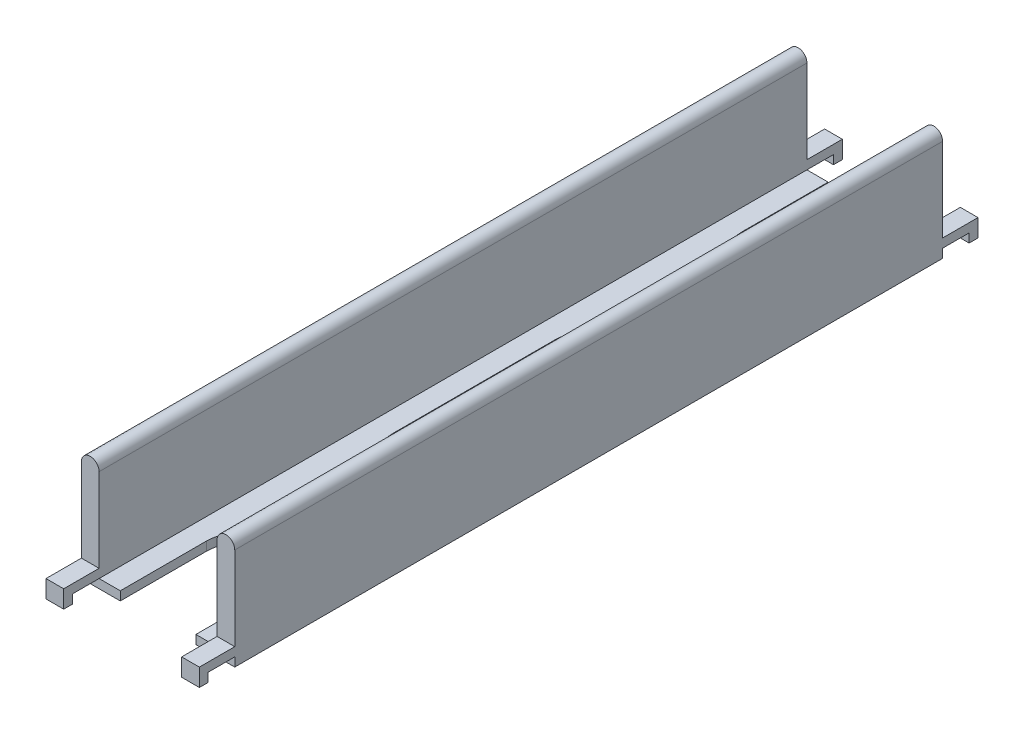
SolidWorks part; units mm, degrees
ref_plane "Front Plane" through (0, 0, 0) normal (0, 0, 1) x (1, 0, 0)
ref_plane "Top Plane" through (0, 0, 0) normal (0, 1, 0) x (1, 0, 0)
ref_plane "Right Plane" through (0, 0, 0) normal (1, 0, 0) x (0, 0, -1)
sketch "Sketch1" plane through (0, 0, 0) normal (0, 1, 0) x (1, 0, 0)
  line L0 (-3.3333, 20) -> (-3.3333, -20)
  line L1 (-4.3333, -20) -> (4.3333, -20)
  line L2 (-4.3333, -20) -> (-4.3333, 20)
  line L3 (-4.3333, 20) -> (4.3333, 20)
  line L4 (4.3333, -20) -> (4.3333, 20)
  line L5 (-4.3333, -20) -> (4.3333, 20) construction
  line L6 (-4.3333, 20) -> (4.3333, -20) construction
  line L7 (3.3333, 20) -> (3.3333, -20)
  point P0 (0, 0)
  dimension "D1" = 8.6667
  dimension "D2" = 40
  dimension "D3" = 1
  dimension "D4" = 1
extrude "Boss-Extrude1" add sketch "Sketch1" along normal blind 0.5 contours L7 L3 L0 L1 region at (0, 0, 0)
extrude "Boss-Extrude2" add sketch "Sketch1<3>" along normal blind 6.23 contours L3 L2 L1 L0 | L3 L7 L1 L4 region at (-3.8333, 0, 0) region at (3.8333, 0, 0)
sketch "Sketch1<3>" plane through (0, 0, 0) normal (0, 1, 0) x (1, 0, 0) same geometry as "Sketch1"
sketch "Sketch2" plane through (0, 0, 20) normal (0, 0, 1) x (1, 0, 0)
  line L0 (-3.3333, 6.23) -> (-3.3333, 0.5) construction
  line L1 (-3.3333, 1) -> (-4.3333, 1)
  line L2 (-3.3333, 1) -> (-3.3333, 0.5)
  line L3 (-3.3333, 0.5) -> (-4.3333, 0.5)
  line L4 (-4.3333, 1) -> (-4.3333, 0.5)
  line L5 (-4.3333, 6.23) -> (-4.3333, 0) construction
  line L6 (-4.3333, 0) -> (4.3333, 0) construction
  line L7 (0, 0.5) -> (0, 3.8059) construction
  line L8 (-3.3333, 0.5) -> (3.3333, 0.5) construction
  line L9 (3.3333, 0.5) -> (4.3333, 0.5)
  line L10 (4.3333, 1) -> (4.3333, 0.5)
  line L11 (3.3333, 1) -> (4.3333, 1)
  line L12 (3.3333, 1) -> (3.3333, 0.5)
  dimension "D1" = 0.5
  dimension "D2" = 0.5
extrude "Boss-Extrude3" add sketch "Sketch2" along normal blind 2
sketch "Sketch3" plane through (0, 0.5, 0) normal (0, -1, 0) x (1, 0, 0)
  line L0 (-3.3333, 22) -> (-3.3333, 20) construction
  line L1 (-4.3333, 22) -> (-3.3333, 22)
  line L2 (-4.3333, 22) -> (-4.3333, 21.5)
  line L3 (-4.3333, 21.5) -> (-3.3333, 21.5)
  line L4 (-3.3333, 22) -> (-3.3333, 21.5)
  line L5 (0, 20) -> (0, 20.9823) construction
  line L6 (-4.3333, 20) -> (4.3333, 20) construction
  line L7 (4.3333, 21.5) -> (3.3333, 21.5)
  line L8 (3.3333, 22) -> (3.3333, 21.5)
  line L9 (4.3333, 22) -> (3.3333, 22)
  line L10 (4.3333, 22) -> (4.3333, 21.5)
  dimension "D1" = 0.5
extrude "Boss-Extrude4" add sketch "Sketch3" along normal blind 0.5
sketch "Sketch4" plane through (0, 0.5, 0) normal (0, 1, 0) x (1, 0, 0)
  line L0 (-3.3333, 0) -> (3.3333, 0) construction
  line L1 (-3.3333, 20) -> (-3.3333, -20) construction
  line L2 (3.3333, 20) -> (3.3333, -20) construction
ref_plane "Plane5" through (0, 0, 0) normal (0, 0, 1) x (1, 0, 0)
mirror "Mirror1" about plane through (0, 0, 0) normal (0, 0, 1) of "Boss-Extrude4", "Boss-Extrude3"
sketch "Sketch5" plane through (0, 0, 20) normal (0, 0, 1) x (1, 0, 0)
  line L0 (-4.3333, 5.73) -> (-4.3333, 6.23)
  line L2 (-4.3333, 6.23) -> (-3.3333, 6.23)
  line L3 (-3.3333, 6.23) -> (-3.3333, 5.73)
  line L4 (0, 0.5) -> (0, 4.6805) construction
  line L5 (-3.3333, 0.5) -> (3.3333, 0.5) construction
  line L6 (3.3333, 6.23) -> (3.3333, 5.73)
  line L7 (4.3333, 5.73) -> (4.3333, 6.23)
  line L8 (4.3333, 6.23) -> (3.3333, 6.23)
  arc A0 (-3.3333, 5.73) -> (-4.3333, 5.73) centre (-3.8333, 5.73) ccw
  arc A1 (3.3333, 5.73) -> (4.3333, 5.73) centre (3.8333, 5.73) cw
  line M3 (-3.3333, 1) -> (-3.3333, 6.23)
  line M4 (-3.3333, 6.23) -> (-4.3333, 6.23)
  line M5 (-4.3333, 6.23) -> (-4.3333, 1)
extrude "Cut-Extrude1" cut sketch "Sketch5" against normal through all contours A0 L2 M5 | A0 M3 M4 | L6 A1 L8 | L8 A1 L7 region at (-3.445, 6.1183, 20) region at (-4.2216, 6.1183, 20) region at (3.445, 6.1183, 20) region at (4.2216, 6.1183, 20)
sketch "Sketch6" plane through (0, 0.5, 0) normal (0, 1, 0) x (1, 0, 0)
  line L0 (0, 4.5611) -> (0, -4.5611) construction
  line L1 (2.1357, 4.5611) -> (2.1357, -4.5611)
  line L2 (-2.1357, 4.5611) -> (-2.1357, -4.5611)
  line L3 (0, 24.8625) -> (0, 15.1375) construction
  line L4 (2.1357, 24.8625) -> (2.1357, 15.1375)
  line L5 (-2.1357, 24.8625) -> (-2.1357, 15.1375)
  line L6 (-3.3333, 20) -> (3.3333, 20) construction
  line L7 (0, 0) -> (-0.4386, 0) construction
  line L8 (0, -24.8625) -> (0, -15.1375) construction
  line L9 (2.1357, -24.8625) -> (2.1357, -15.1375)
  line L10 (-2.1357, -24.8625) -> (-2.1357, -15.1375)
  arc A0 (2.1357, 4.5611) -> (-2.1357, 4.5611) centre (0, 4.5611) ccw
  arc A1 (-2.1357, -4.5611) -> (2.1357, -4.5611) centre (0, -4.5611) ccw
  arc A2 (2.1357, 24.8625) -> (-2.1357, 24.8625) centre (0, 24.8625) ccw
  arc A3 (-2.1357, 15.1375) -> (2.1357, 15.1375) centre (0, 15.1375) ccw
  arc A4 (2.1357, -24.8625) -> (-2.1357, -24.8625) centre (0, -24.8625) cw
  arc A5 (-2.1357, -15.1375) -> (2.1357, -15.1375) centre (0, -15.1375) cw
  point P3 (0, 0)
  point P10 (0, 20)
  point P21 (0, -20)
extrude "Cut-Extrude2" cut sketch "Sketch6" against normal through all
